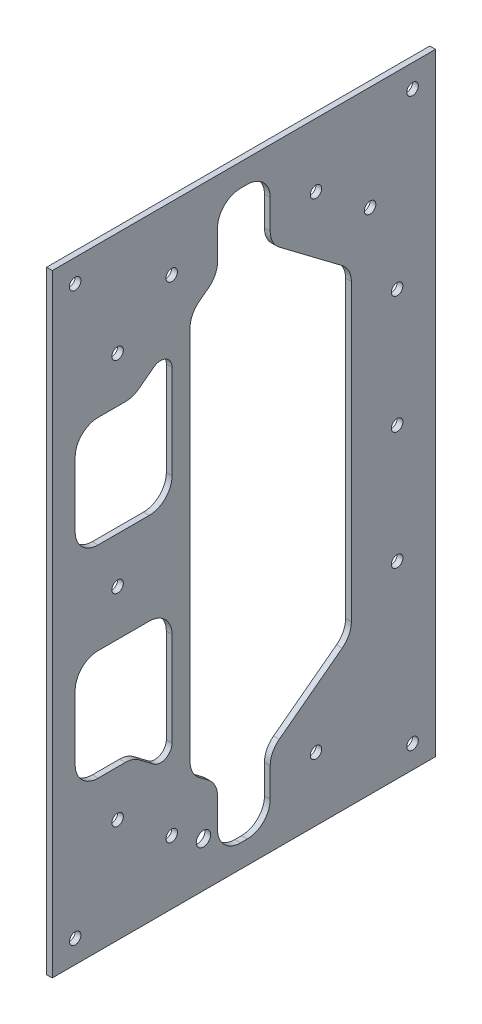
SolidWorks part; units mm, degrees
material "6061-T6 (SS)"
ref_plane "Front Plane" through (0, 0, 0) normal (0, 0, 1) x (1, 0, 0)
ref_plane "Top Plane" through (0, 0, 0) normal (0, 1, 0) x (1, 0, 0)
ref_plane "Right Plane" through (0, 0, 0) normal (1, 0, 0) x (0, 0, -1)
sketch "Sketch1" plane through (0, 0, 0) normal (1, 0, 0) x (0, 0, -1)
  line L0 (0, -169.8625) -> (212.5, -169.8625) construction
  line L1 (0, 0) -> (212.5, 0)
  line L2 (0, 0) -> (0, -339.725)
  line L3 (0, -339.725) -> (212.5, -339.725)
  line L4 (212.5, 0) -> (212.5, -339.725)
  line L5 (153.5, -35.2425) -> (59, -35.2425) construction
  line L6 (191.25, -104.5325) -> (191.25, -169.8625) construction
  line L7 (13.5, -50.2425) -> (59, -50.2425) construction
  line L8 (36.25, -50.2425) -> (36.25, -169.8625) construction
  line L9 (106.25, 0) -> (106.25, -339.725) construction
  line L10 (173.5, -104.5325) -> (191.25, -104.5325) construction
  circle A0 centre (12.7, -12.7) radius 3.175
  circle A1 centre (199.8, -12.7) radius 3.175
  circle A2 centre (66.25, -35.2425) radius 3.175
  circle A3 centre (146.25, -35.2425) radius 3.175
  circle A4 centre (176.25, -57.8625) radius 3.175
  circle A5 centre (36.25, -57.8625) radius 3.175
  circle A6 centre (191.25, -104.5325) radius 3.175
  circle A7 centre (36.25, -169.8625) radius 3.175
  circle A8 centre (191.25, -169.8625) radius 3.175
  circle A9 centre (36.25, -281.8625) radius 3.175
  circle A10 centre (66.25, -304.4825) radius 3.175
  circle A11 centre (12.7, -327.025) radius 3.175
  circle A12 centre (199.8, -327.025) radius 3.175
  circle A13 centre (146.25, -304.4825) radius 3.175
  circle A14 centre (191.25, -235.1925) radius 3.175
  dimension "D1" = 339.725
  dimension "D2" = 212.5
  dimension "D3" = 40
  dimension "D4" = 112
  dimension "D5" = 85
  dimension "D6" = 157.1625
extrude "Boss-Extrude1" add sketch "Sketch1" along normal blind 3.175
sketch "Sketch2" plane through (3.175, 0, 0) normal (1, 0, 0) x (0, 0, -1)
  line L1 (165.85, -88.1617) -> (165.85, -251.5633)
  line L4 (0, 0) -> (0, -339.725)
  line L5 (0, -339.725) -> (212.5, -339.725)
  line L6 (212.5, -339.725) -> (212.5, 0)
  line L7 (212.5, 0) -> (0, 0)
  line L8 (0, 0) -> (0, -339.725)
  line L9 (0, -339.725) -> (212.5, -339.725)
  line L10 (212.5, -339.725) -> (212.5, 0)
  line L11 (212.5, 0) -> (0, 0)
  line L14 (25.4, -144.4625) -> (48.95, -144.4625)
  line L15 (25.4, -83.2625) -> (40.5014, -83.2625)
  line L16 (12.7, -95.9625) -> (12.7, -131.7625)
  line L17 (34.7163, -60.6425) -> (37.7837, -60.6425)
  line L18 (61.65, -70.5625) -> (61.65, -70.522)
  line L19 (61.65, -182.5625) -> (61.65, -157.1625)
  line L20 (36.25, -57.8625) -> (66.25, -35.2425) construction
  line L21 (48.1473, -80.703) -> (86.5959, -51.7127)
  line L22 (91.65, -25.4) -> (91.65, -41.5722)
  line L23 (120.85, -25.4) -> (120.85, -41.5722)
  line L24 (104.35, -12.7) -> (108.15, -12.7)
  line L25 (176.25, -57.8625) -> (146.25, -35.2425) construction
  line L26 (125.9041, -51.7127) -> (160.7959, -78.0212)
  line L27 (0, -169.8625) -> (212.5, -169.8625) construction
  line L28 (176.25, -281.8625) -> (146.25, -304.4825) construction
  line L29 (36.25, -281.8625) -> (66.25, -304.4825) construction
  line L30 (125.9041, -288.0123) -> (160.7959, -261.7038)
  line L31 (104.35, -327.025) -> (108.15, -327.025)
  line L32 (120.85, -314.325) -> (120.85, -298.1528)
  line L33 (91.65, -314.325) -> (91.65, -298.1528)
  line L34 (48.1473, -259.022) -> (86.5959, -288.0123)
  line L35 (61.65, -269.1625) -> (61.65, -269.203)
  line L36 (34.7163, -279.0825) -> (37.7837, -279.0825)
  line L37 (12.7, -243.7625) -> (12.7, -207.9625)
  line L38 (25.4, -256.4625) -> (40.5014, -256.4625)
  line L39 (25.4, -195.2625) -> (48.95, -195.2625)
  circle A0 centre (176.25, -57.8625) radius 3.175 construction
  circle A1 centre (146.25, -35.2425) radius 3.175 construction
  circle A2 centre (66.25, -35.2425) radius 3.175 construction
  circle A3 centre (36.25, -57.8625) radius 3.175 construction
  circle A4 centre (36.25, -169.8625) radius 3.175 construction
  circle A5 centre (36.25, -281.8625) radius 3.175 construction
  circle A6 centre (66.25, -304.4825) radius 3.175 construction
  circle A7 centre (146.25, -304.4825) radius 3.175 construction
  circle A8 centre (191.25, -235.1925) radius 3.175 construction
  circle A9 centre (191.25, -169.8625) radius 3.175 construction
  circle A10 centre (191.25, -104.5325) radius 3.175 construction
  circle A11 centre (176.25, -57.8625) radius 3.175 construction
  circle A12 centre (146.25, -35.2425) radius 3.175 construction
  circle A13 centre (66.25, -35.2425) radius 3.175 construction
  circle A14 centre (36.25, -57.8625) radius 3.175 construction
  circle A15 centre (36.25, -169.8625) radius 3.175 construction
  circle A16 centre (36.25, -281.8625) radius 3.175 construction
  circle A17 centre (66.25, -304.4825) radius 3.175 construction
  circle A18 centre (146.25, -304.4825) radius 3.175 construction
  circle A19 centre (191.25, -235.1925) radius 3.175 construction
  circle A20 centre (191.25, -169.8625) radius 3.175 construction
  circle A21 centre (191.25, -104.5325) radius 3.175 construction
  arc A28 (48.95, -144.4625) -> (61.65, -157.1625) centre (48.95, -157.1625) cw
  arc A29 (12.7, -131.7625) -> (25.4, -144.4625) centre (25.4, -131.7625) ccw
  arc A30 (12.7, -95.9625) -> (25.4, -83.2625) centre (25.4, -95.9625) cw
  arc A33 (165.85, -88.1617) -> (160.7959, -78.0212) centre (153.15, -88.1617) ccw
  arc A34 (125.9041, -51.7127) -> (120.85, -41.5722) centre (133.55, -41.5722) cw
  arc A35 (108.15, -12.7) -> (120.85, -25.4) centre (108.15, -25.4) cw
  arc A36 (104.35, -12.7) -> (91.65, -25.4) centre (104.35, -25.4) ccw
  arc A37 (86.5959, -51.7127) -> (91.65, -41.5722) centre (78.95, -41.5722) ccw
  arc A38 (48.1473, -80.703) -> (40.5014, -83.2625) centre (40.5014, -70.5625) cw
  circle A39 centre (36.25, -281.8625) radius 3.175 construction
  circle A40 centre (66.25, -304.4825) radius 3.175 construction
  circle A41 centre (146.25, -304.4825) radius 3.175 construction
  circle A42 centre (176.25, -281.8625) radius 3.175 construction
  arc A43 (48.1473, -259.022) -> (40.5014, -256.4625) centre (40.5014, -269.1625) ccw
  arc A44 (86.5959, -288.0123) -> (91.65, -298.1528) centre (78.95, -298.1528) cw
  arc A45 (104.35, -327.025) -> (91.65, -314.325) centre (104.35, -314.325) cw
  arc A46 (108.15, -327.025) -> (120.85, -314.325) centre (108.15, -314.325) ccw
  arc A47 (125.9041, -288.0123) -> (120.85, -298.1528) centre (133.55, -298.1528) ccw
  arc A48 (165.85, -251.5633) -> (160.7959, -261.7038) centre (153.15, -251.5633) cw
  arc A49 (12.7, -243.7625) -> (25.4, -256.4625) centre (25.4, -243.7625) ccw
  arc A50 (12.7, -207.9625) -> (25.4, -195.2625) centre (25.4, -207.9625) cw
  arc A51 (48.95, -195.2625) -> (61.65, -182.5625) centre (48.95, -182.5625) ccw
  point P73 (61.65, -83.2625)
  point P78 (61.65, -60.6425)
  point P92 (61.65, -279.0825)
  point P110 (61.65, -169.8625)
  point P114 (165.85, -169.8625)
  point P115 (61.65, -256.4625)
  dimension "D11" = 25.4
  dimension "D13" = 25.4
  dimension "D17" = 12.7
  dimension "D2" = 25.4
  dimension "D7" = 25.4
  dimension "D8" = 25.4
  dimension "D9" = 25.4
  dimension "D14" = 25.4
  dimension "D15" = 12.7
  dimension "D16" = 25.4
  dimension "D1" = 0
extrude "Cut-Extrude1" cut sketch "Sketch2" against normal through all contours L1 L18 L15 A30 L16 A29 L14 A28 L19 A43 region at (3.175, -169.8625, -97.6088)
sketch "Sketch3" plane through (0, 0, 0) normal (-1, 0, 0) x (0, 0, 1)
  line L0 (-212.5, -339.725) -> (-83.8431, -339.725)
  line L1 (0, -339.725) -> (-212.5, -339.725) construction
  line L2 (-83.8431, -339.725) -> (-83.8431, -314.725)
  line L3 (-212.5, 0) -> (-83.8431, 0)
  line L4 (-212.5, 0) -> (0, 0) construction
  circle A0 centre (-83.8431, -314.725) radius 4
  dimension "D4" = 8
  dimension "D1" = 128.6569
  dimension "D2" = 25
  dimension "D3" = 128.6569
extrude "Cut-Extrude2" cut sketch "Sketch3" against normal blind 13.97 contours A0 region at (0, -317.4734, -81.0946)
sketch "Sketch4" plane through (0, 0, 0) normal (-1, 0, 0) x (0, 0, 1)
  line L0 (-83.8431, -314.725) -> (-66.3431, -314.725)
  line L1 (-76.4331, -274.0197) -> (-76.4331, -65.7053)
  line L2 (-48.1473, -259.022) -> (-86.5959, -288.0123) construction
  line L3 (-48.1473, -80.703) -> (-86.5959, -51.7127) construction
  line L4 (0, -339.725) -> (0, 0)
  line L5 (0, 0) -> (-212.5, 0)
  line L6 (-212.5, 0) -> (-212.5, -339.725)
  line L7 (-212.5, -339.725) -> (0, -339.725)
  line L8 (0, -339.725) -> (0, 0)
  line L9 (0, 0) -> (-212.5, 0)
  line L10 (-212.5, 0) -> (-212.5, -339.725)
  line L11 (-212.5, -339.725) -> (0, -339.725)
  line L12 (-66.4331, -131.7625) -> (-66.4331, -79.6562)
  line L13 (-48.95, -144.4625) -> (-53.733, -144.4625)
  line L14 (-48.95, -195.2625) -> (-53.733, -195.2625)
  line L15 (-66.4331, -207.9625) -> (-66.4331, -260.0688)
  line L16 (-56.2601, -265.139) -> (-48.1473, -259.022)
  line L17 (-81.4871, -284.1602) -> (-86.5959, -288.0123)
  line L18 (-81.4871, -55.5648) -> (-86.5959, -51.7127)
  line L19 (-56.2601, -74.586) -> (-48.1473, -80.703)
  line L20 (-81.4871, -55.5648) -> (-56.2601, -74.586)
  line L21 (-56.2601, -265.139) -> (-81.4871, -284.1602)
  line L22 (-61.65, -182.5625) -> (-61.65, -157.1625) construction
  line L23 (-61.65, -182.5625) -> (-61.65, -157.1625)
  circle A0 centre (-83.8431, -314.725) radius 4 construction
  circle A1 centre (-83.8431, -314.725) radius 4
  circle A2 centre (-66.25, -304.4825) radius 3.175 construction
  circle A3 centre (-66.25, -304.4825) radius 3.175
  arc A4 (-66.4331, -131.7625) -> (-53.733, -144.4625) centre (-53.7331, -131.7625) ccw
  arc A5 (-53.733, -195.2625) -> (-66.4331, -207.9625) centre (-53.7331, -207.9625) ccw
  arc A6 (-76.4331, -274.0197) -> (-81.4871, -284.1602) centre (-89.1331, -274.0197) cw
  arc A7 (-66.4331, -260.0688) -> (-56.2601, -265.139) centre (-60.0831, -260.0688) ccw
  arc A8 (-56.2601, -74.586) -> (-66.4331, -79.6562) centre (-60.0831, -79.6562) ccw
  arc A9 (-81.4871, -55.5648) -> (-76.4331, -65.7053) centre (-89.1331, -65.7053) cw
  arc A10 (-61.65, -182.5625) -> (-48.95, -195.2625) centre (-48.95, -182.5625) ccw construction
  arc A11 (-48.95, -144.4625) -> (-61.65, -157.1625) centre (-48.95, -157.1625) ccw construction
  arc A12 (-61.65, -182.5625) -> (-48.95, -195.2625) centre (-48.95, -182.5625) ccw
  arc A13 (-48.95, -144.4625) -> (-61.65, -157.1625) centre (-48.95, -157.1625) ccw
  point P29 (-66.4331, -195.2625)
  point P36 (-76.4331, -280.3495)
  point P39 (-66.4331, -272.8095)
  point P46 (-66.4331, -66.9155)
  point P49 (-76.4331, -59.3755)
  dimension "D6" = 12.7
  dimension "D7" = 12.7
  dimension "D8" = 12.7
  dimension "D9" = 6.35
  dimension "D10" = 6.35
  dimension "D11" = 12.7
  dimension "D2" = 17.5
  dimension "D3" = 10.2425
  dimension "D4" = 10
  dimension "D5" = 7.41
  dimension "D1" = 0
extrude "Boss-Extrude2" add sketch "Sketch4" against normal blind 3.175 contours A13 L13 A4 L12 A8 L20 A9 L1 A6 L21 A7 L15 A5 L14 A12 L23 region at (0, -169.8625, -70.0623)
